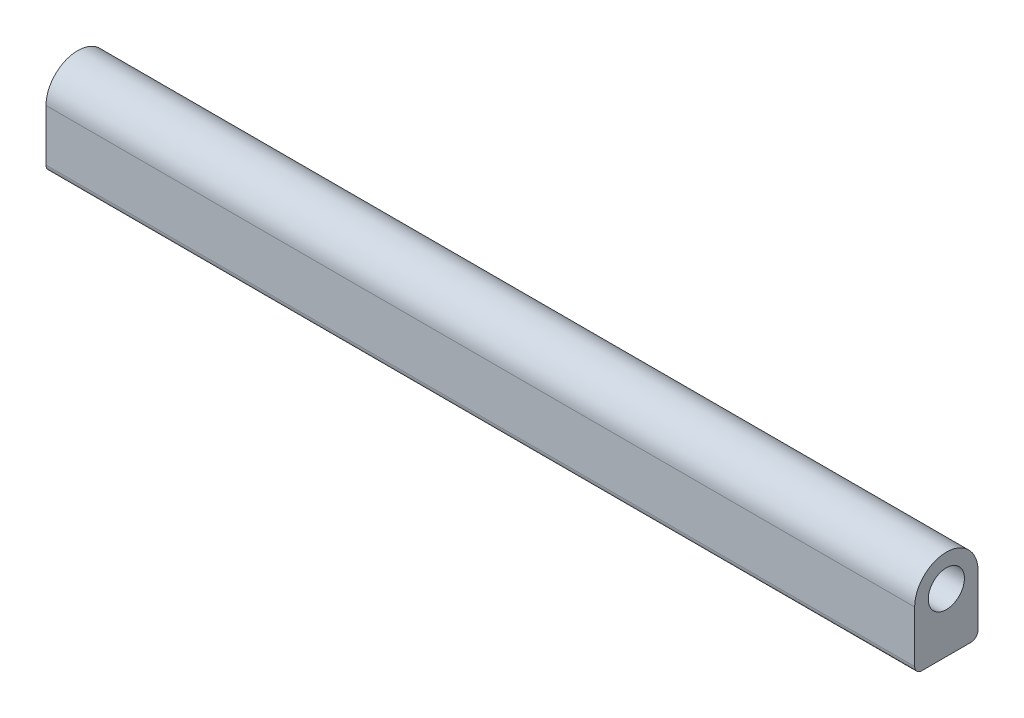
SolidWorks part; units mm, degrees
material "6061 Alloy"
ref_plane "Front Plane" through (0, 0, 0) normal (0, 0, 1) x (1, 0, 0)
ref_plane "Top Plane" through (0, 0, 0) normal (0, 1, 0) x (1, 0, 0)
ref_plane "Right Plane" through (0, 0, 0) normal (1, 0, 0) x (0, 0, -1)
sketch "Sketch1" plane through (0, 0, 0) normal (1, 0, 0) x (0, 0, -1)
  line L0 (-11.1125, 0) -> (-11.1125, -18.0975)
  line L1 (-8.5725, -20.6375) -> (8.5725, -20.6375)
  line L2 (11.1125, -18.0975) -> (11.1125, 0)
  circle A0 centre (0, 0) radius 6.35
  arc A1 (11.1125, 0) -> (-11.1125, 0) centre (0, 0) ccw
  arc A2 (-11.1125, -18.0975) -> (-8.5725, -20.6375) centre (-8.5725, -18.0975) ccw
  arc A3 (8.5725, -20.6375) -> (11.1125, -18.0975) centre (8.5725, -18.0975) ccw
  point P3 (0, 11.1125)
  dimension "D1" = 12.7
  dimension "D4" = 2.54
  dimension "D2" = 22.225
  dimension "D3" = 31.75
extrude "Extrude1" add sketch "Sketch1" along normal blind 152.4 and the other way blind 152.4
hole_wizard "Ø13.0 (13) Diameter Hole1" positions "3DSketch1" profile "Sketch2" hole size "Ø13.0" standard "Ansi Metric"
sketch3d "3DSketch1"
  line L3 (-152.4, -20.6375, 0) -> (-112.5, -20.6375, 0) construction
  line L4 (-152.4, -20.6375, 8.5725) -> (-152.4, -20.6375, -8.5725) construction
  line L5 (-112.5, -20.6375, 0) -> (-37.5, -20.6375, 0) construction
  line L6 (-37.5, -20.6375, 0) -> (37.5, -20.6375, 0) construction
  line L7 (37.5, -20.6375, 0) -> (112.5, -20.6375, 0) construction
  line L8 (112.5, -20.6375, 0) -> (152.4, -20.6375, 0) construction
  line L9 (152.4, -20.6375, 8.5725) -> (152.4, -20.6375, -8.5725) construction
  point P0 (-112.5, -20.6375, 0)
  point P2 (-37.5, -20.6375, 0)
  point P4 (37.5, -20.6375, 0)
  point P6 (112.5, -20.6375, 0)
sketch "Sketch2" plane through (-112.5, -20.6375, 0) normal (1, 0, 0) x (0, 0, -1)
  line L0 (0, 0) -> (0, 24.5421)
  line L1 (0, 24.5421) -> (6.5, 20.6365)
  line L2 (6.5, 20.6365) -> (6.5, 0)
  line L5 (6.5, 0) -> (0, 0)
  line L10 (0, 24.5421) -> (-6.5, 20.6365) construction
  line L11 (0, -6.35) -> (0, 107.95) construction
  dimension "Hole Dia." = 13
  dimension "Hole Depth" = 20.6365
  dimension "Drill Angle" = 118
